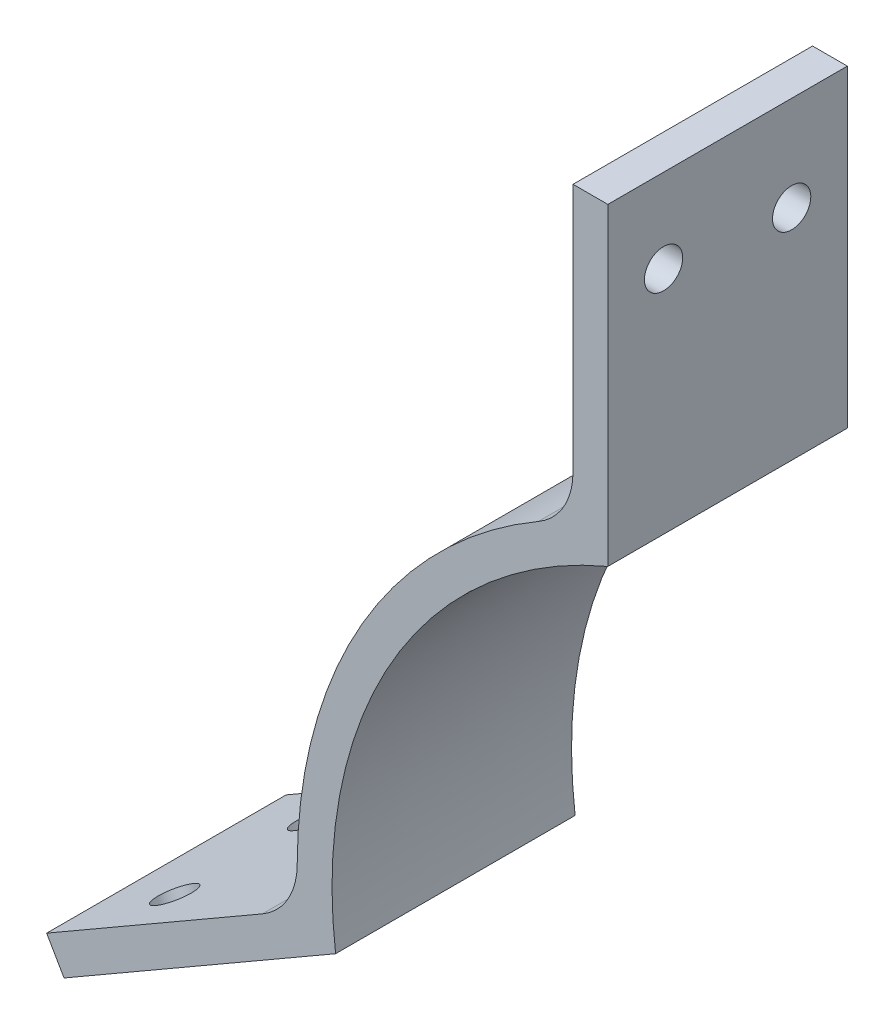
SolidWorks part; units mm, degrees
ref_plane "Front Plane" through (0, 0, 0) normal (0, 0, 1) x (1, 0, 0)
ref_plane "Top Plane" through (0, 0, 0) normal (0, 1, 0) x (1, 0, 0)
ref_plane "Right Plane" through (0, 0, 0) normal (1, 0, 0) x (0, 0, -1)
sketch "Sketch1" plane through (0, 0, 0) normal (0, 0, 1) x (1, 0, 0)
  line L1 (25, 64.615) -> (-25, 64.615)
  line L2 (25, 64.615) -> (25, 104.615)
  line L3 (25, 104.615) -> (-25, 104.615)
  line L4 (-25, 64.615) -> (-25, 104.615)
  line L5 (25, 64.615) -> (-25, 104.615) construction
  line L6 (25, 104.615) -> (-25, 64.615) construction
  line L14 (-25, 59.5827) -> (-25, 104.615)
  line L15 (-30, 104.615) -> (-30, 57.2285)
  line L16 (-25, 104.615) -> (-30, 104.615)
  line L17 (0, 84.615) -> (0, 104.615) construction
  line L18 (25, 59.5827) -> (25, 104.615)
  line L19 (30, 104.615) -> (30, 57.2285)
  line L20 (25, 104.615) -> (30, 104.615)
  line L21 (43.4582, -53.9581) -> (78.0992, -73.9581)
  line L22 (43.4582, -53.9581) -> (68.4582, -10.6569)
  line L23 (68.4582, -10.6569) -> (103.0992, -30.6569)
  line L24 (78.0992, -73.9581) -> (103.0992, -30.6569)
  line L25 (103.0992, -30.6569) -> (105.5992, -26.3267)
  line L26 (105.5992, -26.3267) -> (64.5613, -2.6335)
  line L27 (64.1001, -8.1407) -> (103.0992, -30.6569)
  line L28 (39.1001, -51.442) -> (78.0992, -73.9581)
  line L29 (75.5992, -78.2883) -> (34.5613, -54.595)
  line L30 (78.0992, -73.9581) -> (75.5992, -78.2883)
  line L31 (-68.4582, -10.6569) -> (-103.0992, -30.6569)
  line L32 (-68.4582, -10.6569) -> (-43.4582, -53.9581)
  line L33 (-43.4582, -53.9581) -> (-78.0992, -73.9581)
  line L34 (-103.0992, -30.6569) -> (-78.0992, -73.9581)
  line L35 (-78.0992, -73.9581) -> (-75.5992, -78.2883)
  line L36 (-75.5992, -78.2883) -> (-34.5613, -54.595)
  line L37 (-39.1001, -51.442) -> (-78.0992, -73.9581)
  line L38 (-64.1001, -8.1407) -> (-103.0992, -30.6569)
  line L39 (-105.5992, -26.3267) -> (-64.5613, -2.6335)
  line L40 (-103.0992, -30.6569) -> (-105.5992, -26.3267)
  line L41 (0, 84.615) -> (0, 0) construction
  line L42 (0, 0) -> (-90.5992, -52.3075) construction
  line L43 (-90.5992, -52.3075) -> (0, 0) construction
  line L44 (0, 0) -> (73.2787, -42.3075) construction
  circle A0 centre (0, 0) radius 64.615 construction
  circle A1 centre (0, 0) radius 64.615
  circle A2 centre (0, 0) radius 69.615
  point P3 (0, 84.615)
  dimension "D1" = 129.23
  dimension "D5" = 5
  dimension "D2" = 50
  dimension "D3" = 40
  dimension "D6" = 5
  dimension "D7" = 120
  dimension "D8" = 40
  dimension "D4" = 3
extrude "Boss-Extrude2" add sketch "Sketch1" along normal blind 34.4 contours L15 A2 L39 A1 | L4 A2 L15 A1 L14 | A2 L14 L16 L15 | L39 A2 L31 L38 A1 | A2 L39 L40 L38 region at (-27.5153, 61.1845, 0) region at (-27.522, 84.2696, 0) region at (-56.6416, 32.7021, 0) region at (-66.745, -6.7633, 0) region at (-86.7407, -18.3, 0)
fillet "Fillet1" radius 10 2 edges at (-69.403, -5.4288, 17.2) (-30, 62.8192, 17.2)
sketch "Sketch2" plane through (-15, 25.9808, 0) normal (-0.5, 0.866, 0) x (0.866, 0.5, 0)
  line L0 (-104.615, -26.4) -> (-68.8371, -26.4) construction
  line L1 (-104.615, -34.4) -> (-104.615, 0) construction
  line L2 (-68.8371, -34.4) -> (-68.8371, 0) construction
  line L3 (-68.8371, -26.4) -> (-92.615, -26.4) construction
  line L4 (-92.615, -26.4) -> (-91.0052, -8) construction
  line L6 (-104.615, 0) -> (-68.8371, 0) construction
  dimension "D1" = 85
  dimension "D3" = 8
  dimension "D4" = 18.4
  dimension "D5" = 12
sketch "Sketch3" plane through (-30, 0, 0) normal (-1, 0, 0) x (0, 0, 1)
  line L0 (26.4, 104.615) -> (26.4, 68.8371) construction
  line L1 (34.4, 104.615) -> (0, 104.615) construction
  line L2 (0, 68.8371) -> (34.4, 68.8371) construction
  line L3 (34.4, 104.615) -> (34.4, 68.8371) construction
  line L4 (8, 104.615) -> (8, 68.8371) construction
  line L5 (0, 104.615) -> (0, 68.8371) construction
  line L6 (26.4, 92.615) -> (8, 91.0052) construction
  point P12 (26.4, 92.615)
  point P13 (26.4, 92.615)
  dimension "D1" = 8
  dimension "D2" = 8
  dimension "D3" = 12
  dimension "D4" = 95
hole_wizard "M5 Clearance Hole1" positions "3DSketch1" profile "Sketch4" hole size "M5" standard "ISO"
sketch3d "3DSketch1"
  point P0 (-30, 91.0052, 8)
  point P3 (-30, 92.615, 26.4)
  point P6 (-95.2069, -20.3267, 26.4)
  point P9 (-93.8128, -19.5218, 8)
sketch "Sketch4" plane through (-30, 91.0052, 8) normal (0, 1, 0) x (0, 0, 1)
  line L0 (0, 0) -> (0, 11.6524)
  line L1 (0, 11.6524) -> (2.75, 10)
  line L2 (2.75, 10) -> (2.75, 0)
  line L5 (2.75, 0) -> (0, 0)
  line L10 (0, 11.6524) -> (-2.75, 10) construction
  line L11 (0, -6.35) -> (0, 107.95) construction
  dimension "Hole Dia." = 5.5
  dimension "Hole Depth" = 10
  dimension "Drill Angle" = 118
sketch "Sketch6" plane through (-30, 0, 0) normal (-1, 0, 0) x (0, 0, 1)
  line L0 (26.4, 92.615) -> (8, 91.0052) construction
  line L1 (30.9763, 82.0101) -> (3.4237, 82.0101)
  line L2 (30.9763, 82.0101) -> (30.9763, 101.6101)
  line L3 (30.9763, 101.6101) -> (3.4237, 101.6101)
  line L4 (3.4237, 82.0101) -> (3.4237, 101.6101)
  line L5 (30.9763, 82.0101) -> (3.4237, 101.6101) construction
  line L6 (30.9763, 101.6101) -> (3.4237, 82.0101) construction
  point P0 (17.2, 91.8101)
  dimension "D1" = 19.6
